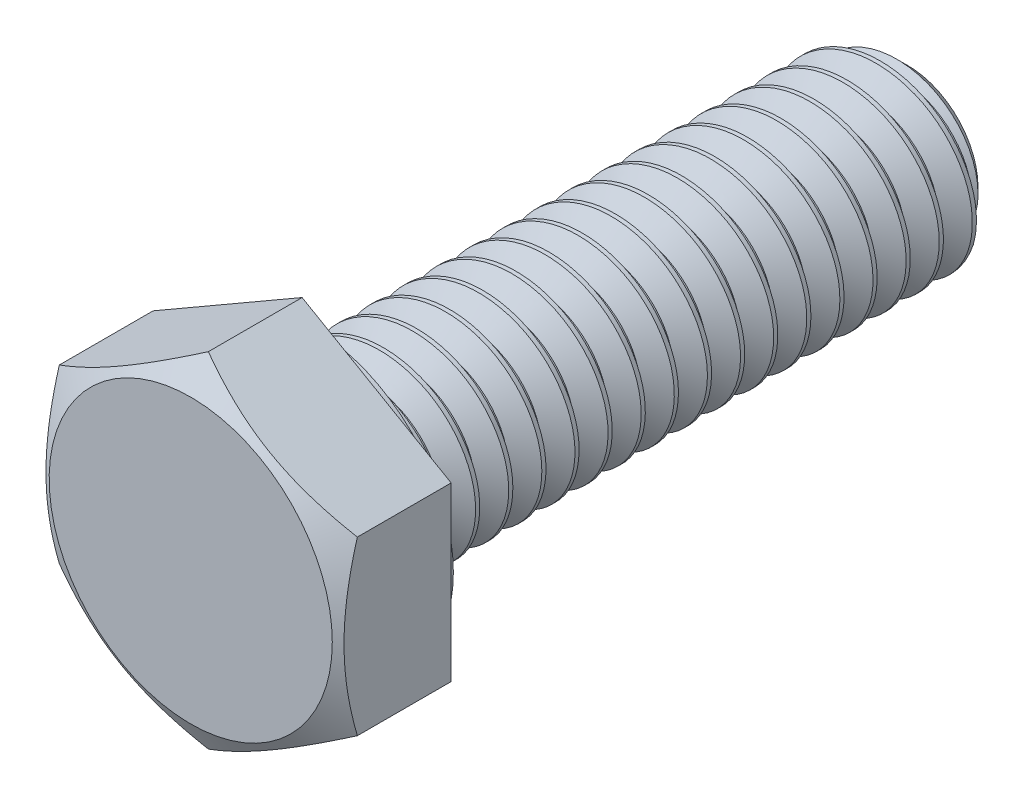
SolidWorks part; units mm, degrees
ref_plane "Front Plane" through (0, 0, 0) normal (0, 0, 1) x (1, 0, 0)
ref_plane "Top Plane" through (0, 0, 0) normal (0, 1, 0) x (1, 0, 0)
ref_plane "Right Plane" through (0, 0, 0) normal (1, 0, 0) x (0, 0, -1)
sketch "Sketch1" plane through (0, 0, 0) normal (1, 0, 0) x (0, 0, -1)
  line L0 (-15.2797, 0) -> (15.2797, 0) construction
  line L1 (15.2797, 3.9751) -> (15.2797, -3.9751) construction
  line L2 (-15.2797, 6.35) -> (-15.2797, -6.35) construction
  line L3 (-10.1203, -6.35) -> (-10.1203, 6.35) construction
  point P7 (13.8686, 0)
  point P10 (-10.1203, 0)
  point P11 (10.3408, -3.9751)
  point P12 (7.6597, 0)
  point P17 (-2.5003, 0)
  dimension "Length" = 25.4
  dimension "Head Height" = 5.1594
  dimension "Screw Size Decimal Equivalent" = 7.9502
  dimension "Head Width" = 12.7
  dimension "Thread Pitch" = 1.4111
  dimension "D1" = 4.9389
  dimension "D2" = 7.62
  dimension "D3" = 7.62
sketch "Sketch2" plane through (0, 0, 0) normal (0, 0, 1) x (1, 0, 0)
  line L1 (0, 7.3323) -> (-6.35, 3.6662) construction
  line L2 (-6.35, 3.6662) -> (-6.35, -3.6662) construction
  line L3 (-6.35, -3.6662) -> (0, -7.3323) construction
  line L4 (0, -7.3323) -> (6.35, -3.6662) construction
  line L5 (6.35, -3.6662) -> (6.35, 3.6662) construction
  line L6 (6.35, 3.6662) -> (0, 7.3323) construction
  circle A0 centre (0, 0) radius 6.35 construction
sketch "Sketch3" plane through (0, 0, 0) normal (1, 0, 0) x (0, 0, -1)
  line L0 (-15.2797, 0) -> (-15.2797, 6.0325)
  line L1 (-14.5292, 7.3323) -> (-10.5331, 7.3323)
  line L2 (-10.5331, 7.3323) -> (-10.5331, 6.0325)
  line L4 (-10.5331, 6.0325) -> (-10.1203, 6.0325)
  line L5 (-10.1203, 6.0325) -> (-10.1203, 3.9751)
  line L6 (-10.1203, 3.9751) -> (14.2919, 3.9751)
  line L7 (15.2797, 2.9873) -> (15.2797, 0)
  line L8 (-15.2797, 0) -> (15.2797, 0) construction
  line L9 (-15.2797, 6.0325) -> (-14.5292, 7.3323)
  line L10 (-15.2797, 0) -> (15.2797, 0)
  line L11 (-15.2797, 6.35) -> (-15.2797, -6.35) construction
  line L12 (-15.2797, 6.0325) -> (-10.5331, 6.0325) construction
  line L13 (-15.2797, 0) -> (-20.0263, 0) construction
  line L14 (14.2919, 3.9751) -> (15.2797, 2.9873)
  line L15 (-10.1203, -6.35) -> (-10.1203, 6.35) construction
  dimension "D2" = 30
  dimension "D3" = 12.065
  dimension "D4" = 45
  dimension "D5" = 0.9878
  dimension "D1" = 0.4127
revolve "Revolve1" add sketch "Sketch3" angle 360 about L0
sketch "Sketch4" plane through (0, 0, 15.2797) normal (0, 0, 1) x (1, 0, 0)
  line L0 (6.35, 3.6662) -> (0, 7.3323) construction
  line L1 (6.35, -3.6662) -> (6.35, 3.6662) construction
  line L2 (0, -7.3323) -> (6.35, -3.6662) construction
  line L3 (-6.35, -3.6662) -> (0, -7.3323) construction
  line L4 (-6.35, 3.6662) -> (-6.35, -3.6662) construction
  line L5 (0, 7.3323) -> (-6.35, 3.6662) construction
  line L6 (6.35, 3.6662) -> (0, 7.3323)
  line L7 (6.35, -3.6662) -> (6.35, 3.6662)
  line L8 (0, -7.3323) -> (6.35, -3.6662)
  line L9 (-6.35, -3.6662) -> (0, -7.3323)
  line L10 (-6.35, 3.6662) -> (-6.35, -3.6662)
  line L11 (0, 7.3323) -> (-6.35, 3.6662)
extrude "Cut-Extrude1" cut sketch "Sketch4" against normal through all flip side to cut
ref_plane "Plane1" through (0, 0, 10.1203) normal (0, 0, -1) x (-1, 0, 0)
split "Split1" trim tools "Plane1" bodies to split 105 resulting bodies 106 107
sketch "Sketch5" plane through (0, 0, -15.2797) normal (0, 0, -1) x (-1, 0, 0)
  circle A0 centre (0, 0) radius 3.9751
curve "Helix/Spiral1" pitch 1.4111 height 26.8111 radius 3.9751 centre (0, 0, -15.2797) axis (0, 0, 1) start towards (0, 1, 0)
sketch "Sketch7" plane through (0, 0, 0) normal (1, 0, 0) x (0, 0, -1)
  line L0 (15.1915, 4.1279) -> (15.897, 2.9058) construction
  line L1 (15.897, 2.9058) -> (16.6026, 4.1279) construction
  line L2 (16.6026, 4.1279) -> (15.1915, 4.1279) construction
  line L3 (15.2797, 3.9751) -> (16.5144, 3.9751) construction
  line L4 (15.897, 4.1279) -> (15.897, 3.9751) construction
  line L5 (15.897, 3.9751) -> (15.897, 3.0586) construction
  line L6 (15.897, 3.0586) -> (15.897, 2.9058) construction
  line L7 (15.8089, 3.0586) -> (15.9852, 3.0586)
  line L8 (15.2356, 4.0515) -> (16.5585, 4.0515)
  line L9 (15.9852, 3.0586) -> (16.5585, 4.0515)
  line L10 (15.8089, 3.0586) -> (15.2356, 4.0515)
  point P12 (15.897, 4.0515)
  dimension "D1" = 1.4111
  dimension "D2" = 0.1764
sweep "Cut-Sweep1" cut profiles "Sketch7" path "Helix/Spiral1" align with end faces yes
sketch "Sketch11" plane through (0, 0, 10.1203) normal (0, 0, 1) x (1, 0, 0)
  circle A1 centre (0, 0) radius 3.9751
extrude "Boss-Extrude2" add sketch "Sketch11" against normal through all draft 30
equation "\"D3@Sketch3\"=\"Head Width@Sketch1\"*0.95"
equation "\"D5@Sketch3\"=\"Thread Pitch@Sketch1\"*0.7"
equation "\"D4@Helix/Spiral1\"=\"Thread Pitch@Sketch1\""
equation "\"D3@Helix/Spiral1\"=\"Length@Sketch1\"+\"Thread Pitch@Sketch1\""
equation "\"D2@Sketch7\"=\"D1@Sketch7\"/8"
equation "\"D1@Sketch7\"=\"Thread Pitch@Sketch1\""
equation "\"D1@Sketch3\"=\"Head Height@Sketch1\"*0.08"
equation "\"D1@Sketch1\"=\"Thread Pitch@Sketch1\"*3.5"
equation "\"D2@Sketch1\"=\"Length@Sketch1\"*0.3"
equation "\"D3@Sketch1\"=\"D2@Sketch1\""
